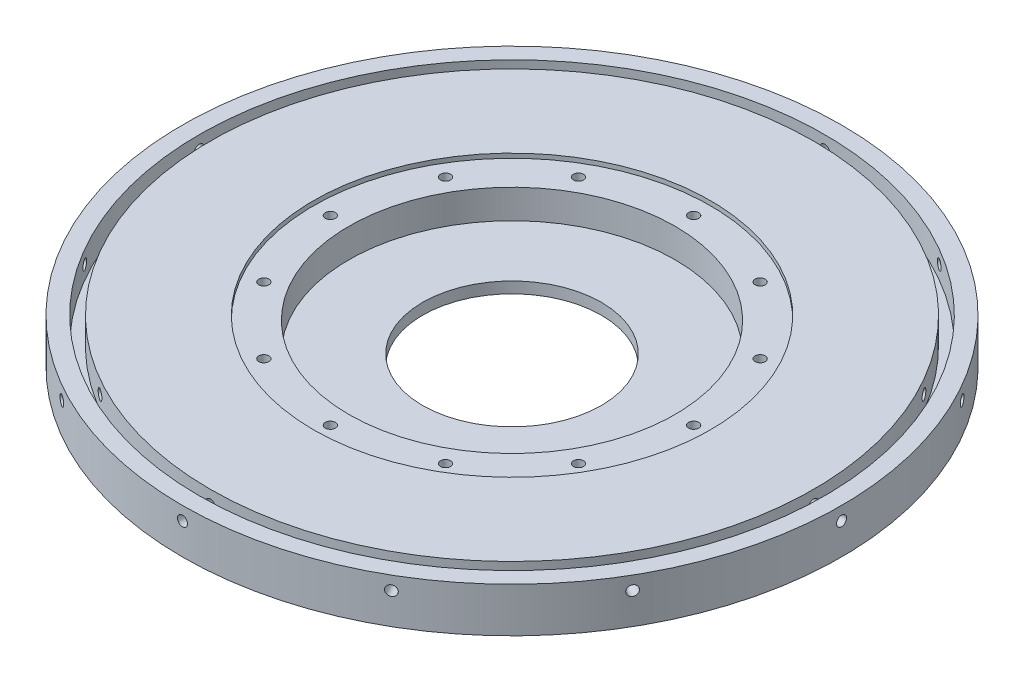
SolidWorks part; units mm, degrees
material "6061-T6 (SS)"
ref_plane "Front Plane" through (0, 0, 0) normal (0, 0, 1) x (1, 0, 0)
ref_plane "Top Plane" through (0, 0, 0) normal (0, 1, 0) x (1, 0, 0)
ref_plane "Right Plane" through (0, 0, 0) normal (1, 0, 0) x (0, 0, -1)
sketch "Sketch1" plane through (0, 0, 0) normal (0, 1, 0) x (1, 0, 0)
  line L5 (0, 0) -> (127.635, 0)
  line L6 (0, 0) -> (0, 127.635)
  line L7 (0, 127.635) -> (127.635, 127.635)
  line L8 (127.635, 0) -> (127.635, 127.635)
  dimension "D1" = 127.635
  dimension "D2" = 127.635
extrude "Boss-Extrude1" add sketch "Sketch1" along normal blind 9.525 contours L5 L8 L7 L6
sketch "Sketch13" plane through (0, 9.525, 0) normal (0, 1, 0) x (1, 0, 0)
  circle A0 centre (63.8175, 63.8175) radius 93.6625
  dimension "D1" = 187.325
extrude "Boss-Extrude2" add sketch "Sketch13" against normal blind 12.7 contours A0
sketch "Sketch6" [suppressed] plane through (127.635, 0, 0) normal (1, 0, 0) x (0, 0, -1)
  circle A0 centre (4.7625, 4.7625) radius 1.3526
  dimension "D1" = 2.7051
extrude "6-32 hole1" [suppressed] cut sketch "Sketch6" against normal blind 12.7
sketch "Sketch7" [suppressed] plane through (0, 0, -127.635) normal (0, 0, -1) x (-1, 0, 0)
  circle A0 centre (-122.8725, 4.7625) radius 1.3525
  dimension "D1" = 2.7051
sketch "Sketch8" [suppressed] plane through (0, 0, 0) normal (-1, 0, 0) x (0, 0, 1)
  circle A0 centre (-122.8725, 4.7625) radius 1.3525
  dimension "D1" = 2.7051
sketch "Sketch9" [suppressed] plane through (0, 0, 0) normal (0, 0, 1) x (1, 0, 0)
  circle A0 centre (4.7625, 4.7625) radius 1.3526
  dimension "D1" = 2.7051
sketch "Sketch5" plane through (0, 9.525, 0) normal (0, 1, 0) x (1, 0, 0)
  circle A0 centre (63.8175, 63.8175) radius 46.355
  circle A1 centre (63.8175, 63.8175) radius 93.6625 construction
  dimension "D1" = 92.71
extrude "Cut-Extrude1" cut sketch "Sketch5" against normal blind 9.525
sketch "Sketch11" plane through (0, 9.525, 0) normal (0, 1, 0) x (1, 0, 0)
  line L0 (63.8175, 63.8175) -> (63.8175, 115.443) construction
  circle A0 centre (63.8175, 115.443) radius 1.4351
  dimension "D2" = 2.8702
  dimension "D1" = 51.6255
extrude "Cut-Extrude3" cut sketch "Sketch11" against normal through all contours A0
pattern_circular "CirPattern1" count 12 over 360 about axis through (63.8175, 9.525, -63.8175) along (0, 1, 0) of "Cut-Extrude3"
sketch "Sketch12" plane through (0, 9.525, 0) normal (0, 1, 0) x (1, 0, 0)
  circle A0 centre (63.8175, 63.8175) radius 56.4198
  dimension "D1" = 112.8395
extrude "Cut-Extrude4" cut sketch "Sketch12" against normal blind 1.27
sketch "Sketch15" plane through (0, 9.525, 0) normal (0, 1, 0) x (1, 0, 0)
  line L0 (63.8175, 63.8175) -> (-29.845, 63.8175) construction
  line L1 (0, -39.1057) -> (0, 39.1057) construction
  line L2 (-20.0025, 63.8175) -> (-25.0825, 63.8175)
  line L3 (-8.7458, 105.7742) -> (-13.2051, 108.2104)
  line L4 (-8.7458, 105.7742) -> (-20.0025, 63.8175) construction
  circle A0 centre (63.8175, 63.8175) radius 56.4198 construction
  arc A1 (-20.0025, 63.8175) -> (-8.7458, 105.7742) centre (63.8175, 63.8175) cw
  arc A2 (-25.0825, 63.8175) -> (-13.2051, 108.2104) centre (63.8175, 63.8175) cw
  circle A3 centre (63.8175, 63.8175) radius 93.6625 construction
  point P0 (63.8175, 63.8175)
  point P11 (-14.3741, 84.7959)
  dimension "D1" = 46.482
  dimension "D2" = 88.9
  dimension "D3" = 83.82
  dimension "D4" = 43.942
sketch "Sketch16" plane through (0, 9.525, 0) normal (0, 1, 0) x (1, 0, 0)
  circle A0 centre (63.8175, 63.8175) radius 88.9
  circle A1 centre (63.8175, 63.8175) radius 85.725
  dimension "D1" = 177.8
  dimension "D2" = 171.45
extrude "Cut-Extrude5" cut sketch "Sketch16" against normal blind 7.62
sketch "Sketch18" plane through (0, 8.255, 0) normal (0, 1, 0) x (1, 0, 0)
  line L0 (63.8175, 185.7252) -> (63.8175, -48.6103) construction
ref_plane "Plane1" through (63.8175, 0, 0) normal (-1, 0, 0) x (0, 0, 1)
ref_plane "Plane2" through (0, 0, 29.845) normal (0, 0, 1) x (1, 0, 0)
sketch "Sketch17" plane through (0, 0, 29.845) normal (0, 0, 1) x (1, 0, 0)
  line L0 (63.8175, 103.0287) -> (63.8175, -103.0287) construction
  line L1 (157.48, 9.525) -> (-29.845, 9.525) construction
  circle A0 centre (63.8175, 5.715) radius 1.4351
  dimension "D1" = 2.8702
  dimension "D2" = 3.81
extrude "Cut-Extrude6" cut sketch "Sketch17" against normal blind 15.24
pattern_circular "CirPattern2" count 12 over 360 about axis through (63.8175, -3.175, -63.8175) along (0, 1, 0) of "Cut-Extrude6" reverse direction yes
sketch "Sketch19" plane through (0, -3.175, 0) normal (0, -1, 0) x (1, 0, 0)
  circle A0 centre (63.8175, -63.8175) radius 25.4
  dimension "D1" = 50.8
extrude "Cut-Extrude7" cut sketch "Sketch19" against normal blind 87.63
